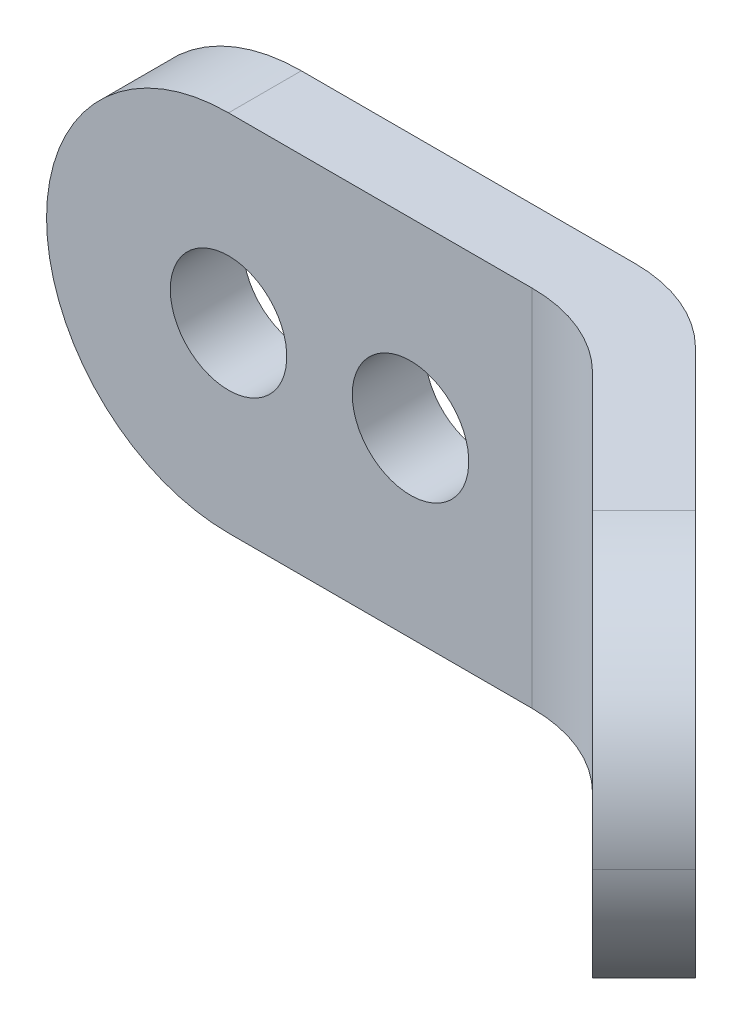
SolidWorks part; units mm, degrees
ref_plane "正面" through (0, 0, 0) normal (0, 0, 1) x (1, 0, 0)
ref_plane "平面" through (0, 0, 0) normal (0, 1, 0) x (1, 0, 0)
ref_plane "右側面" through (0, 0, 0) normal (1, 0, 0) x (0, 0, -1)
sketch "ｽｹｯﾁ1" plane through (0, 0, 0) normal (0, 0, 1) x (1, 0, 0)
  line L0 (-12.5, 0) -> (12.5, 0) construction
  line L1 (12.5, -5) -> (-12.5, -5)
  line L2 (12.5, -5) -> (12.5, 5)
  line L3 (12.5, 5) -> (-12.5, 5)
  line L4 (-12.5, -5) -> (-12.5, 5)
  line L5 (12.5, -5) -> (-12.5, 5) construction
  line L6 (12.5, 5) -> (-12.5, -5) construction
  circle A0 centre (-7.5, 0) radius 1.6
  circle A1 centre (-2.5, 0) radius 1.6
  point P0 (0, 0)
  dimension "D3" = 5
  dimension "D4" = 5
  dimension "D5" = 3.2
  dimension "D1" = 25
  dimension "D2" = 10
extrude "ﾎﾞｽ - 押し出し1" add sketch "ｽｹｯﾁ1" along normal blind 10
sketch "ｽｹｯﾁ2" plane through (0, -5, 0) normal (0, -1, 0) x (1, 0, 0)
  line L0 (2.5, 10) -> (10.5, 10)
  line L1 (2.5, 2) -> (-12.5, 2)
  line L2 (2.5, 2) -> (2.5, 10) construction
  line L3 (2.5, 10) -> (-12.5, 10)
  line L4 (-12.5, 2) -> (-12.5, 10)
  line L5 (2.5, 2) -> (-12.5, 10) construction
  line L6 (2.5, 10) -> (-12.5, 2) construction
  line L7 (-12.5, 10) -> (12.5, 10) construction
  line L8 (10.5, 10) -> (2.5, 2)
  line L9 (3.3284, 0) -> (12.5, 9.1716)
  line L10 (-12.5, 0) -> (12.5, 0) construction
  line L11 (12.5, 10) -> (12.5, 0) construction
  line L12 (3.3284, 0) -> (12.5, 0)
  line L13 (12.5, 0) -> (12.5, 9.1716)
  point P0 (-5, 6)
  point P5 (6.5, 6)
  dimension "D1" = 8
  dimension "D2" = 45
  dimension "D3" = 15
  dimension "D4" = 2
extrude "ｶｯﾄ - 押し出し1" cut sketch "ｽｹｯﾁ2" against normal up to next
sketch "ｽｹｯﾁ3" plane through (0, -5, 0) normal (0, -1, 0) x (1, 0, 0)
  line L0 (10.5, 10) -> (11.9142, 8.5858)
  line L1 (12.5, 9.1716) -> (3.3284, 0) construction
  line L2 (11.9142, 8.5858) -> (12.5, 9.1716)
  line L3 (12.5, 9.1716) -> (12.5, 10)
  line L4 (12.5, 10) -> (10.5, 10)
extrude "ｶｯﾄ - 押し出し2" cut sketch "ｽｹｯﾁ3" against normal up to next
sketch "ｽｹｯﾁ4" plane through (1.6642, 0, -1.6642) normal (0.7071, 0, -0.7071) x (-0.7071, 0, -0.7071)
  line L0 (-2.3536, 0) -> (-14.4957, 0) construction
  line L1 (-14.4957, 5) -> (-14.4957, -5) construction
  line L2 (-2.3536, 5) -> (-2.3536, -5) construction
  circle A0 centre (-11.2036, 0) radius 2
  point P6 (0, 0)
  point P9 (0, 0)
  dimension "D1" = 4
  dimension "D2" = 8.85
extrude "ｶｯﾄ - 押し出し3" cut sketch "ｽｹｯﾁ4" against normal through all
fillet "ﾌｨﾚｯﾄ1" radius 4 2 edges at (3.3284, 0, 0) (2.5, 0, 2)
fillet "ﾌｨﾚｯﾄ2" radius 5 4 edges at (11.2071, 5, 9.2929) (11.2071, -5, 9.2929) (-12.5, -5, 1) (-12.5, 5, 1)
